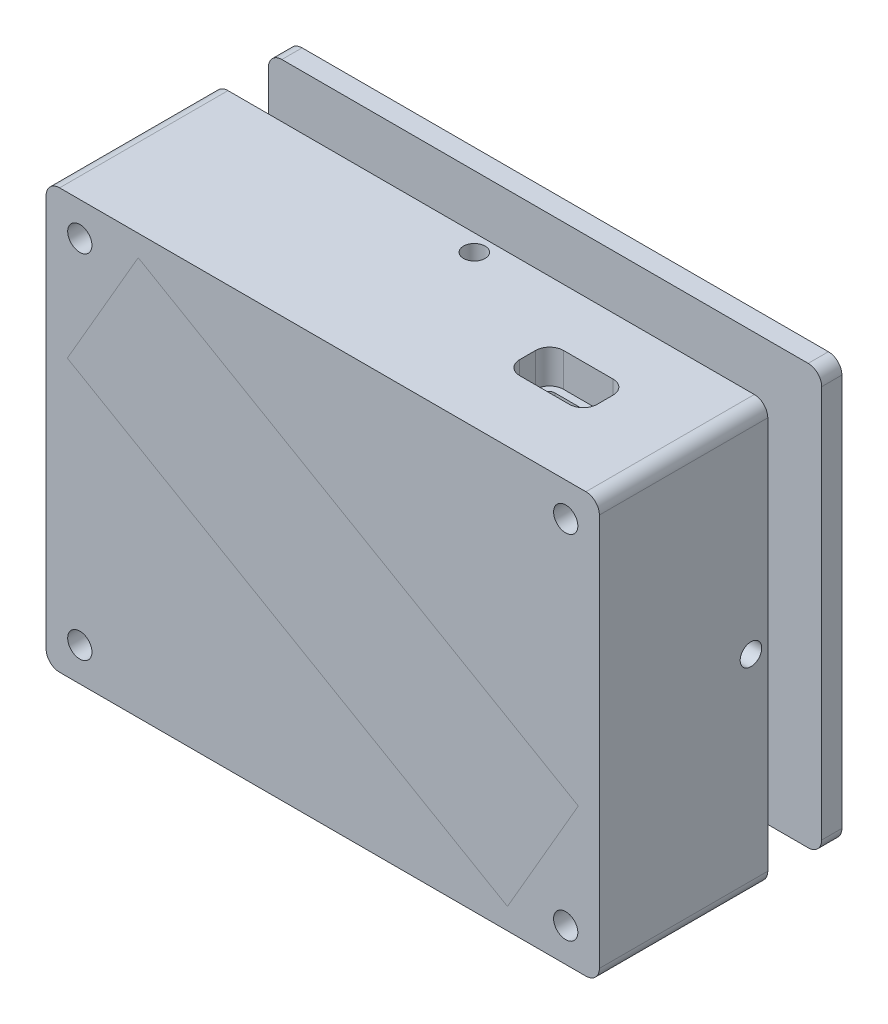
SolidWorks part; units mm, degrees
ref_plane "Front Plane" through (0, 0, 0) normal (0, 0, 1) x (1, 0, 0)
ref_plane "Top Plane" through (0, 0, 0) normal (0, 1, 0) x (1, 0, 0)
ref_plane "Right Plane" through (0, 0, 0) normal (1, 0, 0) x (0, 0, -1)
sketch "Sketch1" plane through (0, 0, 0) normal (0, 0, 1) x (1, 0, 0)
  line L0 (-52.3117, 23.3251) -> (-52.3117, -26.6749)
  line L1 (-52.3117, -26.6749) -> (17.6883, -26.6749)
  line L2 (17.6883, -26.6749) -> (17.6883, 23.3251)
  line L3 (17.6883, 23.3251) -> (-52.3117, 23.3251)
  dimension "D1" = 50
  dimension "D2" = 70
extrude "Boss-Extrude1" add sketch "Sketch1" along normal blind 2
sketch "Sketch2" plane through (0, 0, 2) normal (0, 0, 1) x (1, 0, 0)
  line L0 (-42.7906, 27.3251) -> (-53.3117, 9.1507)
  line L1 (-53.3117, 9.1507) -> (12.0295, -28.6749)
  line L2 (12.0295, -28.6749) -> (22.5506, -10.5005)
  line L3 (22.5506, -10.5005) -> (-42.7906, 27.3251)
  line L4 (-52.3117, 23.3251) -> (-52.3117, -26.6749) construction
  line L5 (17.6883, 23.3251) -> (-52.3117, 23.3251) construction
  line L7 (-52.3117, -26.6749) -> (17.6883, -26.6749) construction
  dimension "D1" = 21
  dimension "D2" = 75.5
  dimension "D3" = 1
  dimension "D4" = 4
  dimension "D5" = 2
extrude "Boss-Extrude2" add sketch "Sketch2" along normal blind 21
sketch "Sketch3" plane through (0, 0, 0) normal (0, 0, -1) x (-1, 0, 0)
  line L0 (-22.6795, 27.4751) -> (-22.6795, -28.8149)
  line L1 (-22.6795, -28.8149) -> (53.4617, -28.8149)
  line L2 (53.4617, -28.8149) -> (53.4617, 27.4751)
  line L3 (53.4617, 27.4751) -> (-22.6795, 27.4751)
  dimension "D1" = 0.129
  dimension "D2" = 0.14
  dimension "D3" = 0.15
  dimension "D4" = 0.15
extrude "Extrude-Thin1" add sketch "Sketch3" along normal blind 10 and the other way blind 23 separate body thin thin type one direction wall 3
sketch "Sketch4" plane through (0, 0, 23) normal (0, 0, 1) x (1, 0, 0)
  line L0 (-42.7906, 27.3251) -> (-53.3117, 9.1507)
  line L1 (-53.3117, 9.1507) -> (12.0295, -28.6749)
  line L2 (12.0295, -28.6749) -> (22.5506, -10.5005)
  line L3 (22.5506, -10.5005) -> (-42.7906, 27.3251)
  line L4 (-53.4617, 27.4751) -> (-53.4617, -28.8149)
  line L5 (-53.4617, -28.8149) -> (22.6795, -28.8149)
  line L6 (22.6795, -28.8149) -> (22.6795, 27.4751)
  line L7 (22.6795, 27.4751) -> (22.6795, -28.8149) construction
  line L8 (22.6795, 27.4751) -> (-53.4617, 27.4751)
extrude "Boss-Extrude3" add sketch "Sketch4" against normal blind 6
fillet "Fillet1" radius 2 4 edges at (25.6795, 30.4751, 6.5) (25.6795, -31.8149, 6.5) (-56.4617, -31.8149, 6.5) (-56.4617, 30.4751, 6.5)
sketch "Sketch5" plane through (0, 0, -10) normal (0, 0, -1) x (-1, 0, 0)
  line L4 (-25.6795, 28.4751) -> (-25.6795, -29.8149) construction
  line L5 (-25.6795, 28.4751) -> (-25.6795, -29.8149)
  line L6 (54.4617, 30.4751) -> (-23.6795, 30.4751) construction
  line L7 (54.4617, 30.4751) -> (-23.6795, 30.4751)
  line L8 (56.4617, -29.8149) -> (56.4617, 28.4751) construction
  line L9 (56.4617, -29.8149) -> (56.4617, 28.4751)
  line L10 (-23.6795, -31.8149) -> (54.4617, -31.8149) construction
  line L11 (-23.6795, -31.8149) -> (54.4617, -31.8149)
  arc A0 (-23.6795, 30.4751) -> (-25.6795, 28.4751) centre (-23.6795, 28.4751) ccw construction
  arc A1 (-23.6795, 30.4751) -> (-25.6795, 28.4751) centre (-23.6795, 28.4751) ccw
  arc A2 (56.4617, 28.4751) -> (54.4617, 30.4751) centre (54.4617, 28.4751) ccw construction
  arc A3 (56.4617, 28.4751) -> (54.4617, 30.4751) centre (54.4617, 28.4751) ccw
  arc A4 (54.4617, -31.8149) -> (56.4617, -29.8149) centre (54.4617, -29.8149) ccw construction
  arc A5 (54.4617, -31.8149) -> (56.4617, -29.8149) centre (54.4617, -29.8149) ccw
  arc A6 (-25.6795, -29.8149) -> (-23.6795, -31.8149) centre (-23.6795, -29.8149) ccw construction
  arc A7 (-25.6795, -29.8149) -> (-23.6795, -31.8149) centre (-23.6795, -29.8149) ccw
extrude "Boss-Extrude4" add sketch "Sketch5" along normal blind 3 separate body
sketch "Sketch6" plane through (0, 0, 17) normal (0, 0, -1) x (-1, 0, 0)
  line L0 (-16.6795, 27.4751) -> (-22.6795, 22.5325)
  line L1 (-22.6795, 27.4751) -> (53.4617, 27.4751) construction
  line L2 (-22.6795, 27.4751) -> (-22.6795, -28.8149) construction
  line L3 (-22.6795, 22.5325) -> (-22.6795, 27.4751)
  line L4 (-22.6795, 27.4751) -> (-16.6795, 27.4751)
  line L5 (42.7906, 27.3251) -> (53.3117, 9.1507)
  line L6 (53.3117, 9.1507) -> (53.4617, 27.4751)
  line L8 (-12.0295, -28.6749) -> (-22.5506, -10.5005)
  line L11 (53.4617, -25.8149) -> (-7.0891, -25.8149)
  line L12 (53.4617, -28.8149) -> (53.4617, 27.4751) construction
  line L13 (53.3117, 9.1507) -> (-12.0295, -28.6749) construction
  line L15 (53.4617, -28.8149) -> (53.4617, -25.8149)
  line L16 (53.4617, -28.8149) -> (-22.6795, -28.8149) construction
  line L18 (-22.6795, -28.8149) -> (53.4617, -28.8149)
  line L19 (-7.0891, -25.8149) -> (-12.0295, -28.6749)
  line L20 (-22.5506, -10.5005) -> (-22.6795, -10.5005)
  line L21 (-22.6795, -10.5005) -> (-22.6795, -28.8149)
  line L22 (42.7906, 27.3251) -> (42.7906, 27.4751)
  line L23 (42.7906, 27.4751) -> (53.4617, 27.4751)
  dimension "D1" = 6
  dimension "D2" = 3
extrude "Boss-Extrude8" add sketch "Sketch6" along normal blind 10
sketch "Sketch7" plane through (0, 0, -10) normal (0, 0, -1) x (-1, 0, 0)
  line L0 (-28.6149, 33.2878) -> (-28.6149, -37.3908)
  line L1 (-28.6149, -37.3908) -> (75.8219, -37.3908)
  line L2 (75.8219, -37.3908) -> (71.6241, 45.1665)
  line L3 (71.6241, 45.1665) -> (-28.6149, 33.2878)
extrude "Cut-Extrude1" cut sketch "Sketch7" against normal blind 8
sketch "Sketch8" plane through (0, 30.4751, 0) normal (0, 1, 0) x (1, 0, 0)
  line L0 (1.7795, -8.5741) -> (1.7795, -10.9259)
  line L1 (3.8536, -13) -> (11.2055, -13)
  line L2 (13.2795, -10.9259) -> (13.2795, -8.5741)
  line L3 (11.2055, -6.5) -> (3.8536, -6.5)
  line L4 (-54.4617, -23) -> (23.6795, -23) construction
  line L6 (25.6795, 2) -> (25.6795, -23) construction
  arc A0 (11.2055, -13) -> (13.2795, -10.9259) centre (11.2055, -10.9259) ccw
  arc A1 (13.2795, -8.5741) -> (11.2055, -6.5) centre (11.2055, -8.5741) ccw
  arc A2 (3.8536, -13) -> (1.7795, -10.9259) centre (3.8536, -10.9259) cw
  arc A3 (3.8536, -6.5) -> (1.7795, -8.5741) centre (3.8536, -8.5741) ccw
  point P12 (13.2795, -6.5)
  point P15 (1.7795, -13)
  point P18 (1.7795, -6.5)
  dimension "D5" = 2.0741
  dimension "D6" = 2.0741
  dimension "D7" = 2.0741
  dimension "D8" = 2.0741
  dimension "D1" = 11.5
  dimension "D2" = 6.5
  dimension "D3" = 10
  dimension "D4" = 12.4
extrude "Cut-Extrude2" cut sketch "Sketch8" against normal blind 8
extrude "Extrude-Thin2" add sketch "Sketch8<2>" against normal blind 6 thin thin type one direction wall 2
sketch "Sketch8<2>" plane through (0, 30.4751, 0) normal (0, 1, 0) x (1, 0, 0) same geometry as "Sketch8"
sketch "Sketch10" plane through (0, 27.4751, 0) normal (0, -1, 0) x (1, 0, 0)
  line L0 (1.7795, 9.75) -> (13.2795, 9.75) construction
  line L1 (1.7795, 8.5741) -> (1.7795, 10.9259) construction
  line L2 (13.2795, 10.9259) -> (13.2795, 8.5741) construction
  line L3 (7.5295, 13) -> (7.5295, 6.5) construction
  line L4 (3.8536, 13) -> (11.2055, 13) construction
  line L5 (11.2055, 6.5) -> (3.8536, 6.5) construction
  line L6 (3.6795, 11.9) -> (11.3795, 11.9)
  line L7 (12.3795, 10.9) -> (12.3795, 8.6)
  line L8 (11.3795, 7.6) -> (3.6795, 7.6)
  line L9 (2.6795, 8.6) -> (2.6795, 10.9)
  line L10 (1.7795, 8.5741) -> (1.7795, 10.9259)
  line L11 (11.2055, 6.5) -> (3.8536, 6.5)
  line L12 (13.2795, 10.9259) -> (13.2795, 8.5741)
  line L13 (3.8536, 13) -> (11.2055, 13)
  arc A0 (1.7795, 8.5741) -> (3.8536, 6.5) centre (3.8536, 8.5741) ccw construction
  arc A1 (11.2055, 6.5) -> (13.2795, 8.5741) centre (11.2055, 8.5741) ccw construction
  arc A2 (13.2795, 10.9259) -> (11.2055, 13) centre (11.2055, 10.9259) ccw construction
  arc A3 (3.8536, 13) -> (1.7795, 10.9259) centre (3.8536, 10.9259) ccw construction
  arc A4 (1.7795, 8.5741) -> (3.8536, 6.5) centre (3.8536, 8.5741) ccw
  arc A5 (11.2055, 6.5) -> (13.2795, 8.5741) centre (11.2055, 8.5741) ccw
  arc A6 (13.2795, 10.9259) -> (11.2055, 13) centre (11.2055, 10.9259) ccw
  arc A7 (3.8536, 13) -> (1.7795, 10.9259) centre (3.8536, 10.9259) ccw
  arc A8 (11.3795, 11.9) -> (12.3795, 10.9) centre (11.3795, 10.9) cw
  arc A9 (12.3795, 8.6) -> (11.3795, 7.6) centre (11.3795, 8.6) cw
  arc A10 (3.6795, 7.6) -> (2.6795, 8.6) centre (3.6795, 8.6) cw
  arc A11 (3.6795, 11.9) -> (2.6795, 10.9) centre (3.6795, 10.9) ccw
  point P11 (12.3795, 11.9)
  point P27 (2.6795, 7.6)
  point P30 (2.6795, 11.9)
  dimension "D3" = 1
  dimension "D4" = 1
  dimension "D5" = 1
  dimension "D6" = 1
  dimension "D1" = 4.3
  dimension "D2" = 9.7
extrude "Boss-Extrude9" add sketch "Sketch10" along normal blind 1 from offset 2
fillet "Fillet2" radius 3 8 edges at (7.5295, 24.4751, 15) (14.0863, 24.4751, 13.8067) (15.2795, 24.4751, 9.75) (14.0863, 24.4751, 5.6933) (7.5295, 24.4751, 4.5) (0.9728, 24.4751, 5.6933) (0.9728, 24.4751, 13.8067) (-0.2205, 24.4751, 9.75)
sketch "Sketch11" plane through (0, 0, 23) normal (0, 0, 1) x (1, 0, 0)
  line L0 (-51.4617, 30.4751) -> (-51.4617, -31.8149) construction
  line L1 (-54.4617, 30.4751) -> (23.6795, 30.4751) construction
  line L2 (23.6795, -31.8149) -> (-54.4617, -31.8149) construction
  line L3 (20.6795, 30.4751) -> (20.6795, -31.8149) construction
  line L4 (-15.3911, 30.4751) -> (-15.3911, -31.8149) construction
  line L5 (-56.4617, -0.6699) -> (25.6795, -0.6699) construction
  line L6 (-56.4617, -29.8149) -> (-56.4617, 28.4751) construction
  line L7 (25.6795, 28.4751) -> (25.6795, -29.8149) construction
  circle A0 centre (-51.4617, 25.4751) radius 1.8
  circle A1 centre (-51.4617, -26.8149) radius 1.8
  circle A2 centre (20.6795, -26.8149) radius 1.8
  circle A3 centre (20.6795, 25.4751) radius 1.8
  dimension "D3" = 3.6
  dimension "D1" = 5
  dimension "D2" = 5
  dimension "D4" = 5
extrude "Cut-Extrude3" cut sketch "Sketch11" against normal blind 5
sketch "Sketch12" plane through (0, 30.4751, 0) normal (0, 1, 0) x (1, 0, 0)
  line L0 (-15.3911, 2) -> (-15.3911, -23) construction
  line L1 (-54.4617, 2) -> (23.6795, 2) construction
  line L2 (-54.4617, -23) -> (23.6795, -23) construction
  circle A0 centre (-15.3911, -0.5) radius 1.6
  dimension "D1" = 3.2
  dimension "D2" = 2.5
extrude "Cut-Extrude4" cut sketch "Sketch12" against normal through all both and the other way through all
sketch "Sketch13" plane through (25.6795, 0, 0) normal (1, 0, 0) x (0, 0, -1)
  line L0 (-23, -0.6699) -> (2, -0.6699) construction
  line L1 (-23, 28.4751) -> (-23, -29.8149) construction
  line L2 (2, 28.4751) -> (2, -29.8149) construction
  circle A0 centre (-0.5, -0.6699) radius 1.6
  dimension "D1" = 3.2
  dimension "D2" = 2.5
extrude "Cut-Extrude5" cut sketch "Sketch13" against normal through all both
